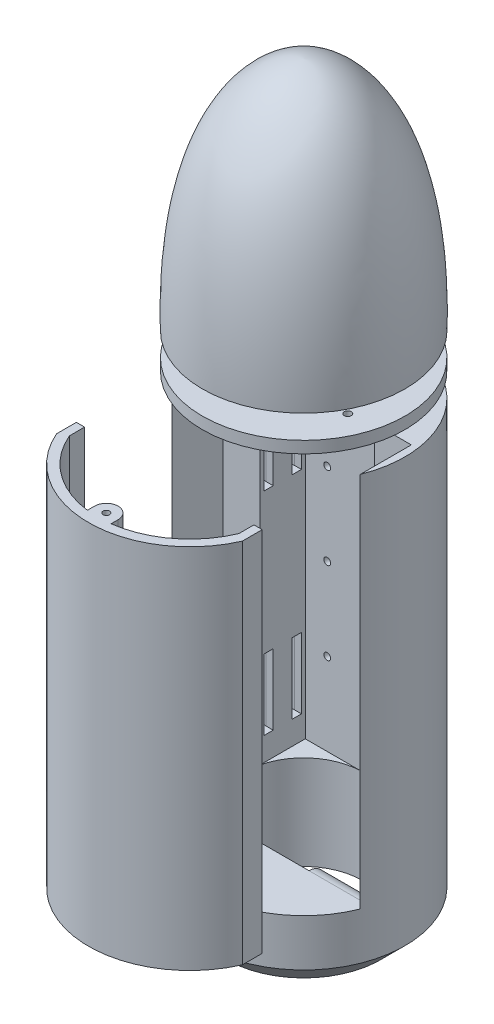
SolidWorks part; units mm, degrees
ref_plane "Front Plane" through (0, 0, 0) normal (0, 0, 1) x (1, 0, 0)
ref_plane "Top Plane" through (0, 0, 0) normal (0, 1, 0) x (1, 0, 0)
ref_plane "Right Plane" through (0, 0, 0) normal (1, 0, 0) x (0, 0, -1)
sketch "Sketch1" plane through (0, 0, 0) normal (0, 1, 0) x (1, 0, 0)
  line L1 (40, -5.75) -> (-40, -5.75)
  line L2 (40, -5.75) -> (40, 5.75)
  line L3 (40, 5.75) -> (-40, 5.75)
  line L4 (-40, -5.75) -> (-40, 5.75)
  line L5 (40, -5.75) -> (-40, 5.75) construction
  line L6 (40, 5.75) -> (-40, -5.75) construction
  circle A0 centre (0, 0) radius 43.0718
  circle A1 centre (0, 0) radius 25
  dimension "D3" = 86.1436
  dimension "D4" = 50
  dimension "D1" = 80
  dimension "D2" = 11.5
extrude "Boss-Extrude1" add sketch "Sketch1" along normal blind 10 contours A0 A1 L3 L2 L1 L4 | L1 A1 region at (0, 0, 13.7788) region at (-41.8536, 0, 0)
sketch "Sketch2" plane through (0, 0, 0) normal (0, -1, 0) x (1, 0, 0)
  circle A0 centre (0, 0) radius 25
  circle A1 centre (0, 0) radius 43.0718
  circle A2 centre (0, 0) radius 22.5
  line M4 (-24.3298, -5.75) -> (-40, -5.75)
  line M5 (-40, -5.75) -> (-40, 5.75)
  arc M7 (24.3298, -5.75) -> (-24.3298, -5.75) centre (0, 0) cw
  line M8 (-40, 5.75) -> (40, 5.75)
  line M9 (40, 5.75) -> (40, -5.75)
  line M10 (40, -5.75) -> (24.3298, -5.75)
  circle M11 centre (0, 0) radius 43.0718
  dimension "D1" = 50
  dimension "D2" = 86.1436
  dimension "D3" = 45
extrude "Boss-Extrude2" add sketch "Sketch2" along normal blind 20 contours A0 M11 M8 M9 M10 M7 M4 M5 | A0 M8 M5 M4 | A0 M10 M9 M8 | A2 M8 region at (-32.3876, 0, 0) region at (32.3876, 0, 0) region at (0, 0, 12.7239) region at (-41.8536, 0, 0)
fillet "Fillet1" radius 7 1 edges at (0, 10, 5.75)
sketch "Sketch3" plane through (0, 10, 0) normal (0, 1, 0) x (1, 0, 0)
  line L0 (-40, -12.75) -> (-40, -15.9744)
  line L1 (40, -12.75) -> (40, -15.9744)
  line L2 (-40, -12.75) -> (-40, 5.75)
  line L3 (-40, 5.75) -> (-24.3298, 5.75)
  line L4 (40, -12.75) -> (40, 5.75)
  line L5 (40, 5.75) -> (24.3298, 5.75)
  circle A0 centre (0, 0) radius 43.0718
  circle A1 centre (0, 0) radius 25
  line M2 (40, 5.75) -> (40, -12.75)
  line M6 (-40, -12.75) -> (-40, 5.75)
  line M7 (-40, 5.75) -> (-24.3298, 5.75)
  arc M8 (-24.3298, 5.75) -> (24.3298, 5.75) centre (0, 0) cw
  line M9 (24.3298, 5.75) -> (40, 5.75)
  circle M10 centre (0, 0) radius 43.0718
  dimension "D1" = 86.1436
  dimension "D2" = 50
extrude "Boss-Extrude3" add sketch "Sketch3" along normal blind 160 contours L1 L0 M2 M10 M6 M7 M8 M9 region at (-40.1044, 10, 14.3622)
ref_plane "Plane1" through (0, 180, 0) normal (0, 1, 0) x (1, 0, 0)
sketch "Sketch18" plane through (0, 170, 0) normal (0, 1, 0) x (1, 0, 0)
  line L1 (-24.3298, 5.75) -> (24.3298, 5.75)
  line L2 (-24.3298, 5.75) -> (-24.3298, 25)
  line L3 (-24.3298, 25) -> (24.3298, 25)
  line L4 (24.3298, 5.75) -> (24.3298, 25)
extrude "Cut-Extrude8" cut sketch "Sketch18" against normal blind 150
sketch "Sketch4" plane through (0, 180, 0) normal (0, 1, 0) x (1, 0, 0)
  line L0 (-24.4949, -5) -> (24.4949, -5)
  circle A0 centre (0, 0) radius 43.0718
  circle A1 centre (0, 0) radius 25
  dimension "D1" = 86.1436
  dimension "D2" = 50
extrude "Boss-Extrude5" add sketch "Sketch4" along normal blind 5 separate body contours A0 A1 | L0 A1 region at (0, 180, 13.3592) region at (-41.8536, 180, 0)
sketch "Sketch6" plane through (0, 10, 0) normal (0, 1, 0) x (1, 0, 0)
  line L1 (-40, -12.75) -> (40, -12.75) construction
  line L2 (40, -12.75) -> (-40, -12.75) construction
  line L3 (0, -12.75) -> (0, -43.0718) construction
  circle A0 centre (-25, -14.75) radius 1.5
  circle A1 centre (0, 0) radius 43.0718 construction
  dimension "D1" = 3
  dimension "D2" = 25
extrude "Cut-Extrude1" cut sketch "Sketch6" against normal blind 10
sketch "Sketch7" plane through (0, 10, 0) normal (0, 1, 0) x (1, 0, 0)
  circle A0 centre (0, -22.1898) radius 5
  dimension "D1" = 10
sketch "Sketch8" plane through (0, 180, 0) normal (0, -1, 0) x (1, 0, 0)
  line L4 (40, 15.9744) -> (40, -5.75)
  line L5 (-40, -5.75) -> (-40, 15.9744)
  line L6 (-24.3298, -5.75) -> (-40, -5.75)
  line L7 (40, -5.75) -> (24.3298, -5.75)
  line L9 (-40, -5.75) -> (-40, 15.9744)
  line L10 (-24.3298, -5.75) -> (-40, -5.75)
  line L11 (40, -5.75) -> (24.3298, -5.75)
  line L15 (-24.3298, -25) -> (-24.3298, -5.75)
  line L16 (-24.3298, -25) -> (-24.3298, -5.75)
  line L17 (24.3298, -25) -> (-24.3298, -25)
  line L18 (24.3298, -25) -> (-24.3298, -25)
  line L19 (24.3298, -5.75) -> (24.3298, -25)
  line L20 (24.3298, -5.75) -> (24.3298, -25)
  line L22 (40, 15.9744) -> (40, -5.75)
  circle A0 centre (30, 11.25) radius 1.5
  circle A1 centre (0, 0) radius 43.0718
  circle A2 centre (0, 0) radius 43.0718
  arc A4 (-40, 15.9744) -> (40, 15.9744) centre (0, 0) ccw
  arc A7 (-40, 15.9744) -> (40, 15.9744) centre (0, 0) ccw
  dimension "D3" = 3
  dimension "D5" = 17
  dimension "D1" = 0
  dimension "D2" = 0
extrude "Cut-Extrude3" cut sketch "Sketch8" against normal through all contours A0 region at (30, 180, 11.25)
sketch "Sketch9" plane through (0, 180, 0) normal (0, -1, 0) x (1, 0, 0)
  line L0 (0, 5) -> (0, 10)
  line L2 (11.5, 10) -> (-11.5, 10)
  line L3 (11.5, 10) -> (11.5, 22)
  line L4 (11.5, 22) -> (-11.5, 22)
  line L5 (-11.5, 10) -> (-11.5, 22)
  line L6 (11.5, 10) -> (-11.5, 22) construction
  line L7 (11.5, 22) -> (-11.5, 10) construction
  line L8 (-24.4949, 5) -> (24.4949, 5) construction
  point P6 (0, 16)
  dimension "D1" = 23
  dimension "D2" = 12
  dimension "D3" = 5
extrude "Cut-Extrude4" cut sketch "Sketch9" against normal through all contours L5 L2 L4 | L3 L4 L2 region at (0, 180, 16)
sketch "Sketch10" plane through (0, 10, 0) normal (0, 1, 0) x (1, 0, 0)
  circle A0 centre (0, -32.0714) radius 1.62
  circle A1 centre (0, 0) radius 43.0718 construction
  dimension "D1" = 3.24
  dimension "D2" = 32.0714
extrude "Cut-Extrude5" cut sketch "Sketch10" against normal blind 5 contours A0
sketch "Sketch12" plane through (0, 0, 0) normal (0, 0, 1) x (1, 0, 0)
  line L0 (0, 195) -> (-43.0718, 195)
  line L1 (0, 195) -> (0, 295)
  line L4 (-38.157, 200) -> (-38.157, 195)
  line L5 (-5, 288.8858) -> (0, 288.8858)
  line L6 (-33.157, 195) -> (-38.157, 200)
  line L7 (-5, 200) -> (-38.157, 200) construction
  line L8 (-5, 200) -> (-5, 288.8858) construction
  line L9 (11.5, 185) -> (-11.5, 185) construction
  line L10 (0, 0) -> (0, 210.2185) construction
  spline S0 degree 3 poles (0, 295) (-18.0651, 293.8361) (-44.9756, 269.8113) (-43.0718, 195) knots 0 0 0 0 1 1 1 1
  spline S1 degree 1 poles (-5, 288.8858) (-38.157, 200) knots 0 0 1 1 construction
  spline S2 degree 3 poles (-5, 288.8858) (-5.4432, 288.7297) (-6.3059, 288.3967) (-8.1035, 287.5804) (-10.3967, 286.2948) (-13.2147, 284.2814) (-17.0056, 280.923) (-21.7223, 275.3682) (-27.0392, 266.2538) (-30.9162, 256.4083) (-33.5245, 247.0682) (-35.1945, 239.3046) (-36.5391, 230.7561) (-37.3562, 222.9573) (-37.8088, 216.2999) (-38.043, 211.0961) (-38.1465, 206.5762) (-38.1721, 202.8602) (-38.1653, 200.9489) (-38.157, 200) knots 0.117292 0.117292 0.117292 0.117292 0.144176 0.17106 0.224828 0.278595 0.332363 0.439899 0.547434 0.654969 0.708737 0.762505 0.816272 0.87004 0.896924 0.923808 0.950692 0.964133 0.977575 0.977575 0.977575 0.977575
  dimension "D1" = 43.0718
  dimension "D2" = 100
  dimension "D5" = 5
  dimension "D6" = 10
revolve "Revolve1" add sketch "Sketch12" angle 360 about L1 region at (-36.4904, 196.6667, 0) region at (-2.5, 289.975, 0)
sketch "Sketch13" plane through (0, 170, 0) normal (0, 1, 0) x (1, 0, 0)
  line L0 (-36, -57.1336) -> (-36, -63.5693)
  line L1 (-40, -57.1336) -> (40, -57.1336)
  line L2 (-40, -15.9744) -> (-40, -64.358)
  line L3 (40, -15.9744) -> (40, -64.358)
  line L4 (36, -57.1336) -> (36, -63.5693)
  line L5 (40, -19.6541) -> (40, -64.358) construction
  line L6 (-36, -19.6541) -> (-36, -63.5693) construction
  line L7 (36, -19.6541) -> (36, -63.5693) construction
  line L8 (-40, -19.6541) -> (-40, -64.358) construction
  line L9 (-36, -63.5693) -> (36, -63.5693)
  line L10 (-39.5, -57.1336) -> (-39.5, -65.5571)
  line L11 (39.5, -57.1336) -> (39.5, -65.5571)
  arc A0 (-40, -64.358) -> (40, -64.358) centre (0, -48.3836) ccw
  arc A1 (-36, -63.5693) -> (36, -63.5693) centre (0, -48.3836) ccw
  arc A2 (40, -15.9744) -> (-40, -15.9744) centre (0, 0) ccw construction
  dimension "D1" = 43.0718
  dimension "D2" = 8.75
  dimension "D4" = 41.1592
  dimension "D5" = 0.5
  dimension "D6" = 0.5
extrude "Boss-Extrude6" add sketch "Sketch13" against normal blind 156 separate body contours A1 L0 L1 L2 A0 L3 L4 region at (-36.8613, 170, 60.3514)
ref_plane "Plane3" through (0, 160, 0) normal (0, 1, 0) x (1, 0, 0)
sketch "Sketch15" plane through (0, 160, 0) normal (0, 1, 0) x (1, 0, 0)
  line L0 (-4.7875, -84.1061) -> (-4.7875, -87.161)
  line L3 (5.2125, -84.1061) -> (-4.7875, -84.1061)
  line L5 (5.2125, -84.1061) -> (5.2125, -87.1061)
  line L10 (-36, -63.5693) -> (-36, -57.1336)
  line L11 (-36, -57.1336) -> (-39.5, -57.1336)
  line L12 (-39.5, -57.1336) -> (-39.5, -65.5571)
  line L13 (39.5, -65.5571) -> (39.5, -57.1336)
  line L14 (39.5, -57.1336) -> (36, -57.1336)
  line L15 (36, -57.1336) -> (36, -63.5693)
  line L16 (-36, -63.5693) -> (-36, -57.1336)
  line L17 (-36, -57.1336) -> (-39.5, -57.1336)
  line L18 (-39.5, -57.1336) -> (-39.5, -65.5571)
  line L19 (39.5, -65.5571) -> (39.5, -57.1336)
  line L20 (39.5, -57.1336) -> (36, -57.1336)
  line L21 (36, -57.1336) -> (36, -63.5693)
  circle A2 centre (0.2125, -84.1061) radius 5
  circle A3 centre (0.2125, -84.1061) radius 1.37
  arc A6 (-36, -63.5693) -> (36, -63.5693) centre (0, -48.3836) ccw
  arc A7 (-39.5, -65.5571) -> (39.5, -65.5571) centre (0, -48.3836) ccw
  arc A8 (-36, -63.5693) -> (36, -63.5693) centre (0, -48.3836) ccw
  arc A9 (-39.5, -65.5571) -> (39.5, -65.5571) centre (0, -48.3836) ccw
  dimension "D3" = 2.74
  dimension "D1" = 3
  dimension "D2" = 10
  dimension "D4" = 0
extrude "Boss-Extrude7" add sketch "Sketch15" along normal up to surface (10 mm away) contours A3 L3 A2 | A3 L3 A2 | A2 | A2 region at (-4.4556, 160, 86.4635) region at (0.2125, 160, 81.859) region at (0.2047, 160, 85.7855) region at (4.8915, 160, 86.4245) up to face at (0, 170, 67.0714)
ref_plane "Plane4" through (0, 110, 0) normal (0, 1, 0) x (1, 0, 0)
sketch "Sketch16" plane through (0, 110, 0) normal (0, 1, 0) x (1, 0, 0)
  line L8 (-36, -63.5693) -> (-36, -57.1336)
  line L9 (-36, -57.1336) -> (-39.5, -57.1336)
  line L10 (-39.5, -57.1336) -> (-39.5, -65.5571)
  line L11 (39.5, -65.5571) -> (39.5, -57.1336)
  line L12 (39.5, -57.1336) -> (36, -57.1336)
  line L13 (36, -57.1336) -> (36, -63.5693)
  line L14 (5.2125, -87.1061) -> (5.2125, -84.1061)
  line L15 (-4.7875, -84.1061) -> (-4.7875, -87.161)
  line L16 (-36, -63.5693) -> (-36, -57.1336)
  line L17 (-36, -57.1336) -> (-39.5, -57.1336)
  line L18 (-39.5, -57.1336) -> (-39.5, -65.5571)
  line L19 (39.5, -65.5571) -> (39.5, -57.1336)
  line L20 (39.5, -57.1336) -> (36, -57.1336)
  line L21 (36, -57.1336) -> (36, -63.5693)
  line L22 (5.2125, -87.1061) -> (5.2125, -84.1061)
  line L23 (-4.7875, -84.1061) -> (-4.7875, -87.161)
  circle A1 centre (0.2125, -84.1061) radius 1.37
  circle A2 centre (0.2125, -84.1061) radius 5
  arc A7 (-36, -63.5693) -> (-4.7875, -87.161) centre (0, -48.3836) ccw
  arc A8 (-39.5, -65.5571) -> (39.5, -65.5571) centre (0, -48.3836) ccw
  arc A9 (5.2125, -87.1061) -> (36, -63.5693) centre (0, -48.3836) ccw
  arc A10 (5.2125, -84.1061) -> (-4.7875, -84.1061) centre (0.2125, -84.1061) ccw
  arc A11 (-36, -63.5693) -> (-4.7875, -87.161) centre (0, -48.3836) ccw
  arc A12 (-39.5, -65.5571) -> (39.5, -65.5571) centre (0, -48.3836) ccw
  arc A13 (5.2125, -87.1061) -> (36, -63.5693) centre (0, -48.3836) ccw
  arc A14 (5.2125, -84.1061) -> (-4.7875, -84.1061) centre (0.2125, -84.1061) ccw
  dimension "D1" = 0
extrude "Boss-Extrude8" add sketch "Sketch16" against normal blind 10 contours A2 A1 | A2 | A2 region at (-24.0788, 110, 80.2406) region at (0.2125, 110, 79.2476)
chamfer "Chamfer1" distance 8.25 angle 45 3 edges at (0.2142, 160, 87.4548) (0.2142, 110, 87.4548) (0.2142, 100, 87.4548)
sketch "Sketch17" plane through (0, 170, 0) normal (0, 1, 0) x (1, 0, 0)
  line L0 (24.3298, 25) -> (-24.3298, 25) construction
  circle A6 centre (-1.2341, 35) radius 3
  dimension "D1" = 10
extrude "Cut-Extrude7" cut sketch "Sketch17" against normal through all and the other way through all contours A6 | A6 region at (-1.2341, 170, -35)
chamfer "Chamfer2" distance 10 distance2 10 1 edges at (0, -20, -43.0718)
sketch "Sketch19" plane through (0, 10, 0) normal (0, 1, 0) x (1, 0, 0)
  line L0 (0, -12.75) -> (0, -1.9529)
  line L1 (-15, -1.9529) -> (15, -1.9529)
  line L2 (-15, -1.9529) -> (-15, -12.75)
  line L3 (-15, -12.75) -> (15, -12.75)
  line L4 (15, -1.9529) -> (15, -12.75)
  line L5 (40, -12.75) -> (-40, -12.75) construction
  line M9 (40, -12.75) -> (-40, -12.75)
  dimension "D1" = 30
extrude "Cut-Extrude9" cut sketch "Sketch19" against normal through all contours L4 L1 L0 M9 | L1 L2 L0 M9 region at (-7.5, 10, 7.3514) region at (7.5, 10, 7.3514)
ref_plane "Plane5" through (0, 150, 0) normal (0, 1, 0) x (1, 0, 0)
sketch "Sketch21" plane through (0, 150, 0) normal (0, 1, 0) x (1, 0, 0)
  line L0 (-24.3298, 5.75) -> (-32.1649, 5.75)
  line L1 (-24.3298, 5.75) -> (-40, 5.75) construction
  line L2 (-24.3298, 5.75) -> (-24.3298, 25)
  line L3 (-24.3298, 15.375) -> (-27.3298, 15.375) construction
  line L4 (-24.3298, 11.375) -> (-27.3298, 11.375)
  line L5 (-24.3298, 19.375) -> (-27.3298, 19.375)
  line L6 (-24.3298, 15.375) -> (-27.3298, 15.375) construction
  line L7 (-24.3298, 7.375) -> (-27.3298, 7.375)
  line L8 (-24.3298, 23.375) -> (-27.3298, 23.375)
  line L9 (0, 0) -> (0, 13.7984) construction
  line L10 (24.3298, 5.75) -> (24.3298, 25)
  line L11 (24.3298, 5.75) -> (32.1649, 5.75)
  line L12 (24.3298, 15.375) -> (27.3298, 15.375) construction
  line L13 (24.3298, 7.375) -> (27.3298, 7.375)
  line L14 (24.3298, 23.375) -> (27.3298, 23.375)
  line L15 (24.3298, 15.375) -> (27.3298, 15.375) construction
  line L16 (24.3298, 11.375) -> (27.3298, 11.375)
  line L17 (24.3298, 19.375) -> (27.3298, 19.375)
  arc A0 (-24.3298, 11.375) -> (-24.3298, 19.375) centre (-24.3298, 15.375) ccw
  arc A1 (-27.3298, 19.375) -> (-27.3298, 11.375) centre (-27.3298, 15.375) ccw
  arc A2 (-24.3298, 7.375) -> (-24.3298, 23.375) centre (-24.3298, 15.375) ccw
  arc A3 (-27.3298, 23.375) -> (-27.3298, 7.375) centre (-27.3298, 15.375) ccw
  arc A4 (24.3298, 7.375) -> (24.3298, 23.375) centre (24.3298, 15.375) cw
  arc A5 (27.3298, 23.375) -> (27.3298, 7.375) centre (27.3298, 15.375) cw
  arc A6 (24.3298, 11.375) -> (24.3298, 19.375) centre (24.3298, 15.375) cw
  arc A7 (27.3298, 19.375) -> (27.3298, 11.375) centre (27.3298, 15.375) cw
  point P9 (-25.8298, 15.375)
  point P14 (-25.8298, 15.375)
  point P29 (25.8298, 15.375)
  point P36 (25.8298, 15.375)
  dimension "D1" = 4
  dimension "D2" = 8
  dimension "D3" = 3
extrude "Cut-Extrude12" cut sketch "Sketch21" against normal blind 30 contours L8 A3 L7 L2 L4 A1 L5 | L17 A7 L16 L10 L13 A5 L14 region at (-25.8298, 150, -7.5692) region at (24.5239, 150, -9.375)
ref_plane "Plane6" through (0, 30, 0) normal (0, 1, 0) x (1, 0, 0)
sketch "Sketch22" plane through (0, 30, 0) normal (0, 1, 0) x (1, 0, 0)
  line L0 (-24.3298, 5.75) -> (-43.4484, 5.75)
  line L1 (-24.3298, 5.75) -> (-24.3298, 25)
  line L2 (-24.3298, 15.375) -> (-27.3298, 15.375) construction
  line L3 (-24.3298, 11.375) -> (-27.3298, 11.375)
  line L4 (-24.3298, 19.375) -> (-27.3298, 19.375)
  line L5 (-24.3298, 15.375) -> (-27.3298, 15.375) construction
  line L6 (-24.3298, 7.375) -> (-27.3298, 7.375)
  line L7 (-24.3298, 23.375) -> (-27.3298, 23.375)
  line L8 (0, -13.8762) -> (0, 13.8762) construction
  line L9 (24.3298, 5.75) -> (24.3298, 25)
  line L10 (24.3298, 5.75) -> (43.4484, 5.75)
  line L11 (24.3298, 15.375) -> (27.3298, 15.375) construction
  line L12 (24.3298, 7.375) -> (27.3298, 7.375)
  line L13 (24.3298, 23.375) -> (27.3298, 23.375)
  line L14 (24.3298, 15.375) -> (27.3298, 15.375) construction
  line L15 (24.3298, 11.375) -> (27.3298, 11.375)
  line L16 (24.3298, 19.375) -> (27.3298, 19.375)
  line L17 (-24.3298, 25) -> (21.6505, 25) construction
  line L18 (-24.3298, 22.4011) -> (-24.3298, 25) construction
  arc A0 (-24.3298, 11.375) -> (-24.3298, 19.375) centre (-24.3298, 15.375) ccw
  arc A1 (-27.3298, 19.375) -> (-27.3298, 11.375) centre (-27.3298, 15.375) ccw
  arc A2 (-24.3298, 7.375) -> (-24.3298, 23.375) centre (-24.3298, 15.375) ccw
  arc A3 (-27.3298, 23.375) -> (-27.3298, 7.375) centre (-27.3298, 15.375) ccw
  arc A4 (24.3298, 7.375) -> (24.3298, 23.375) centre (24.3298, 15.375) cw
  arc A5 (27.3298, 23.375) -> (27.3298, 7.375) centre (27.3298, 15.375) cw
  arc A6 (24.3298, 11.375) -> (24.3298, 19.375) centre (24.3298, 15.375) cw
  arc A7 (27.3298, 19.375) -> (27.3298, 11.375) centre (27.3298, 15.375) cw
  point P5 (-25.8298, 15.375)
  point P10 (-25.8298, 15.375)
  point P24 (25.8298, 15.375)
  point P31 (25.8298, 15.375)
  point P37 (0, 0)
  dimension "D1" = 4
  dimension "D2" = 8
  dimension "D3" = 3
extrude "Cut-Extrude13" cut sketch "Sketch22" along normal blind 30 contours L16 A7 L15 L9 L12 A5 L13 | L7 A3 L6 L1 L3 A1 L4 region at (-25.8298, 30, -7.5692) region at (24.5239, 30, -9.375)
sketch "Sketch24" plane through (0, 0, -25) normal (0, 0, 1) x (1, 0, 0)
  line L0 (0, 190) -> (0, 26.5986) construction
  line L4 (-24.3298, 20) -> (0, 20)
  line L5 (24.3298, 20) -> (24.3298, 170)
  line L6 (24.3298, 170) -> (-24.3298, 170)
  line L7 (-24.3298, 170) -> (-24.3298, 20)
  line L9 (24.3298, 20) -> (24.3298, 170)
  line L10 (24.3298, 170) -> (-24.3298, 170)
  line L11 (-24.3298, 170) -> (-24.3298, 20)
  line L14 (-24.3298, 20) -> (0, 20)
  line L15 (0, 20) -> (24.3298, 20)
  line L16 (0, 20) -> (24.3298, 20)
  circle A0 centre (-15, 160) radius 1.45
  circle A1 centre (15, 160) radius 1.45
  circle A2 centre (15, 125) radius 1.45
  circle A3 centre (15, 90) radius 1.45
  circle A4 centre (15, 55) radius 1.45
  circle A5 centre (-15, 125) radius 1.45
  circle A6 centre (-15, 90) radius 1.45
  circle A7 centre (-15, 55) radius 1.45
  dimension "D1" = 2.9
  dimension "D3" = 10
  dimension "D4" = 15
  dimension "D5" = 2
  dimension "D6" = 4
extrude "Cut-Extrude14" cut sketch "Sketch24" against normal blind 7 contours A1 | A0 | A5 | A2 | A6 | A3 | A4 | A7 region at (-15, 160, -25) region at (15, 160, -25) region at (15, 125, -25) region at (15, 90, -25) region at (15, 55, -25) region at (-15, 125, -25) region at (-15, 90, -25) region at (-15, 55, -25)
equation "\"PhoneWidth\"= 80"
equation "\"PhoneThickness\"= 11.5"
equation "\"OuterDiam\"= ( sqr ( ( \"PhoneWidth\" / 2 ) ^ 2 + ( \"PhoneThickness\" / 2 ) ) + 3 ) * 2"
equation "\"TubeInnerDia\"= 45'Inner tube Diamiter"
equation "\"TubeOuterDia\"= 50'Outer tube dimiter"
equation "\"TubeLength\"= 300'Total length of tube"
equation "\"PhoneHeight\"=150"
equation "\"ServoLength\"= 23"
equation "\"ServoThickness\"= 12"
equation "\"WireDiamiter\"= 2.24"
equation "\"D3@Sketch1\"=\"OuterDiam\""
equation "\"D1@Sketch12\"=\"OuterDiam\"/2"
equation "\"D1@Sketch1\"=\"PhoneWidth\""
equation "\"D2@Sketch1\"=\"PhoneThickness\""
equation "\"D4@Sketch1\"=\"TubeOuterDia\""
equation "\"D3@Sketch2\"=\"TubeInnerDia\""
equation "\"D1@Sketch2\"=\"TubeOuterDia\""
equation "\"D2@Sketch2\"=\"OuterDiam\""
equation "\"D1@Boss-Extrude3\"=\"PhoneHeight\"+10"
equation "\"D2@Sketch4\"=\"TubeOuterDia\""
equation "\"D1@Sketch4\"=\"OuterDiam\""
equation "\"D2@Sketch12\"=\"PhoneHeight\"/1.5"
equation "\"D1@Sketch13\"=\"OuterDiam\"/2"
equation "\"D2@Sketch13\"=(\"PhoneThickness\"/2) + 3"
equation "\"D1@Boss-Extrude6\"=\"PhoneHeight\"+6"
equation "\"Clearence\"= 0.5"
equation "\"D5@Sketch13\"=\"Clearence\""
equation "\"D6@Sketch13\"=\"Clearence\""
equation "\"D2@Sketch6\"=(\"PhoneWidth\"/2)-15"
equation "\"D1@Sketch3\"=\"OuterDiam\""
equation "\"mountingHoleDiameter\"= 2.9"
equation "\"D1@Sketch24\"=\"mountingHoleDiameter\""
equation "\"D1@Cut-Extrude8\"=\"PhoneHeight\""
